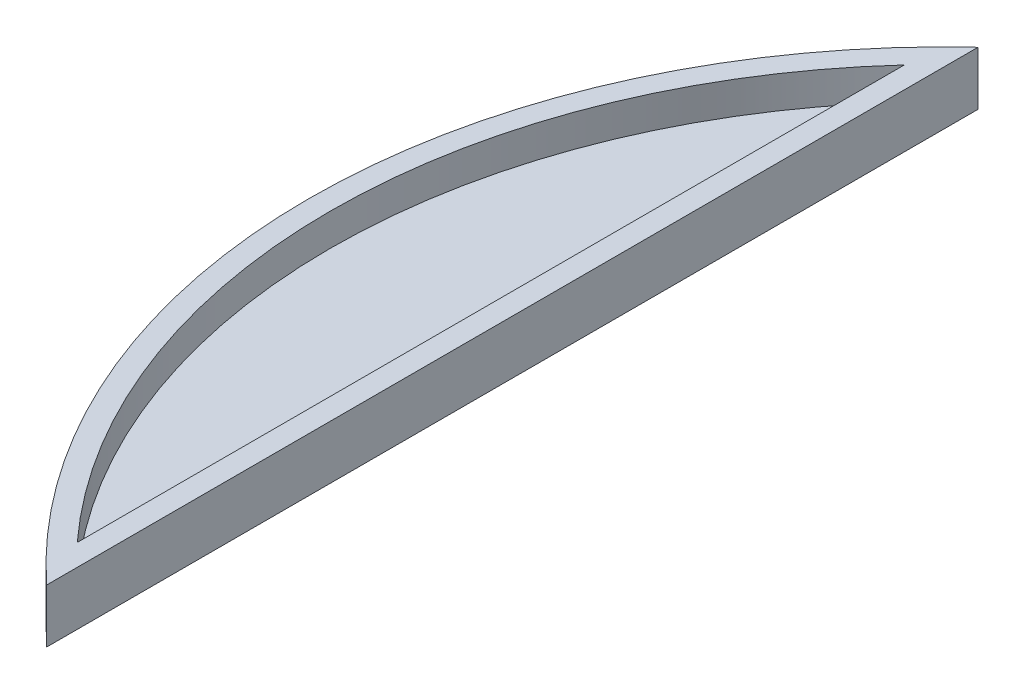
SolidWorks part; units mm, degrees
ref_plane "Front Plane" through (0, 0, 0) normal (0, 0, 1) x (1, 0, 0)
ref_plane "Top Plane" through (0, 0, 0) normal (0, 1, 0) x (1, 0, 0)
ref_plane "Right Plane" through (0, 0, 0) normal (1, 0, 0) x (0, 0, -1)
sketch "Sketch1" plane through (0, 0, 0) normal (0, 1, 0) x (1, 0, 0)
  line L0 (0, 0) -> (0, -109.982)
  circle A0 centre (50.8969, -54.991) radius 74.93
  dimension "D1" = 109.982
  dimension "D2" = 149.86
extrude "Boss-Extrude1" add sketch "Sketch1" along normal blind 6.35 contours L0 A0 region at (-9.759, 0, 54.991)
shell "Shell1" thickness 2.54 removed face at (-12.0165, 6.35, 54.991)
